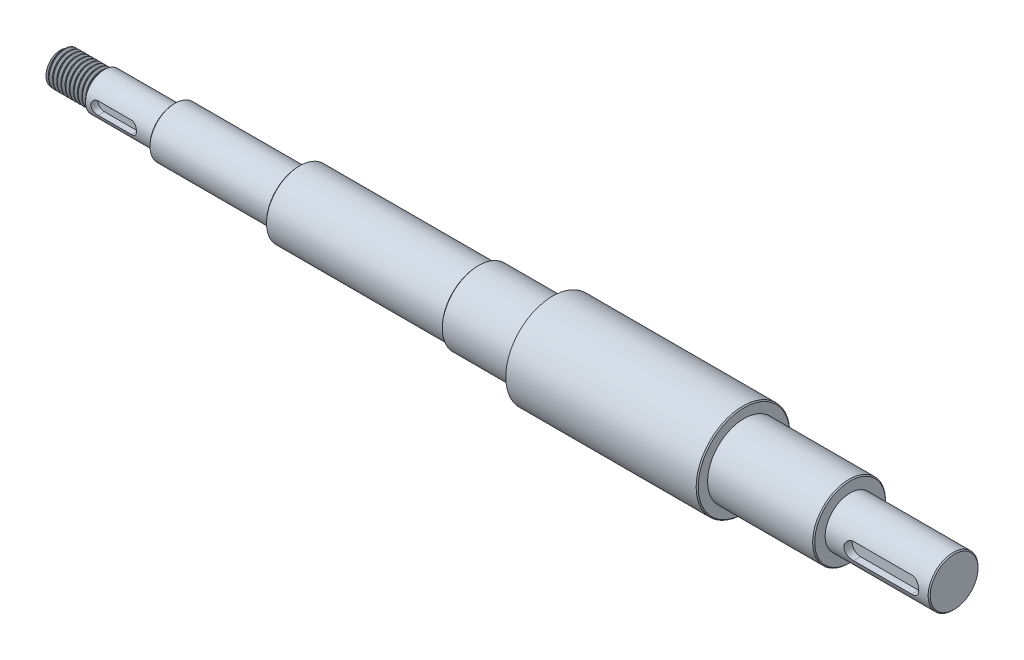
SolidWorks part; units mm, degrees
note: The reader was unsure of these and kept them because the rebuilt part matched: shared geometry of "Sketch2<3>".
ref_plane "Front Plane" through (0, 0, 0) normal (0, 0, 1) x (1, 0, 0)
ref_plane "Top Plane" through (0, 0, 0) normal (0, 1, 0) x (1, 0, 0)
ref_plane "Right Plane" through (0, 0, 0) normal (1, 0, 0) x (0, 0, -1)
sketch "Sketch1" plane through (0, 0, 0) normal (0, 0, 1) x (1, 0, 0)
  line L0 (-214.5, 0) -> (214.5, 0) construction
  line L1 (-214.5, 0) -> (-214.5, 8)
  line L2 (-214.5, 8) -> (-194.5, 8)
  line L3 (-194.5, 8) -> (-194.5, 9)
  line L4 (-194.5, 9) -> (-160.5, 9)
  line L5 (-160.5, 9) -> (-160.5, 12)
  line L6 (-160.5, 12) -> (-100.5, 12)
  line L7 (-100.5, 12) -> (-100.5, 16)
  line L8 (-100.5, 16) -> (-14.5, 16)
  line L9 (-14.5, 16) -> (-14.5, 17.5)
  line L10 (-14.5, 17.5) -> (21.5, 17.5)
  line L11 (21.5, 17.5) -> (21.5, 22.5)
  line L12 (21.5, 22.5) -> (113.5, 22.5)
  line L13 (113.5, 22.5) -> (113.5, 17.5)
  line L14 (113.5, 17.5) -> (164.5, 17.5)
  line L15 (164.5, 17.5) -> (164.5, 12)
  line L16 (164.5, 12) -> (214.5, 12)
  line L17 (214.5, 12) -> (214.5, 0)
  line L18 (214.5, 0) -> (-214.5, 0)
  point P4 (0, 0)
  dimension "D1" = 429
  dimension "D2" = 20
  dimension "D3" = 34
  dimension "D4" = 60
  dimension "D5" = 86
  dimension "D6" = 36
  dimension "D7" = 92
  dimension "D8" = 51
  dimension "D9" = 50
  dimension "D10" = 16
  dimension "D11" = 18
  dimension "D12" = 24
  dimension "D13" = 32
  dimension "D14" = 35
  dimension "D15" = 45
  dimension "D16" = 35
  dimension "D17" = 24
revolve "Revolve1" add sketch "Sketch1" angle 360 about L0
chamfer "Chamfer1" distance 0.5 angle 45 8 edges at (113.5, 0, 22.5) (-214.5, 0, 8) (-194.5, 0, 9) (-160.5, 0, 12) (-100.5, 0, 16) (-14.5, 0, 17.5) (164.5, 0, 17.5) (214.5, 0, 12)
thread "Thread3" pitch 2 start angle 0, offset 1.5, length 20, pitch 2, diameter 16
ref_plane "Plane4" through (-215.5, 0, -8) normal (0, -1, 0) x (0, 0, -1)
sketch "Thread Profile4" plane through (-215.5, 0, -8) normal (0, -1, 0) x (0, 0, -1)
  line L0 (0, 0) -> (0, 2) construction
  line L11 (0, 0) -> (0, 1.75)
  line L12 (0, 1.75) -> (-1.0825, 1.125)
  line L13 (-1.0825, 1.125) -> (-1.0825, 0.625)
  line L15 (-1.0825, 0.625) -> (0, 0)
  line L17 (-1.0825, 0.875) -> (0, 0.875) construction
  point P2 (0, 0)
  dimension "Pitch" = 2
  dimension "Profile_Angle" = 60
  dimension "Profile_Land" = 0.5
  dimension "Profile_Height" = 1.0825
sketch "Sketch2" plane through (0, 0, 0) normal (0, 0, 1) x (1, 0, 0)
  line L0 (-188.5, 0) -> (-172.5, 0) construction
  line L1 (-188.5, 3) -> (-172.5, 3)
  line L2 (-188.5, -3) -> (-172.5, -3)
  line L3 (-160.5, 0) -> (-194, 0) construction
  line L4 (-194.5, 8.5) -> (-194.5, -8.5) construction
  line L5 (214.5, -11.5) -> (214.5, 11.5) construction
  line L8 (177.5, 0) -> (205.5, 0) construction
  line L9 (177.5, 4) -> (205.5, 4)
  line L10 (177.5, -4) -> (205.5, -4)
  arc A0 (-188.5, 3) -> (-188.5, -3) centre (-188.5, 0) ccw
  arc A1 (-172.5, -3) -> (-172.5, 3) centre (-172.5, 0) ccw
  arc A2 (177.5, 4) -> (177.5, -4) centre (177.5, 0) ccw
  arc A3 (205.5, -4) -> (205.5, 4) centre (205.5, 0) ccw
  point P2 (-180.5, 0)
  point P11 (191.5, 0)
  dimension "D1" = 6
  dimension "D3" = 3
  dimension "D4" = 9
  dimension "D6" = 4
  dimension "D2" = 16
  dimension "D5" = 28
extrude "Cut-Extrude5" cut sketch "Sketch2" along normal blind 3.5 from offset 5.5 contours L2 A1 L1 A0
extrude "Cut-Extrude6" cut sketch "Sketch2<3>" along normal blind 4 from offset 8
sketch "Sketch2<3>" plane through (0, 0, 0) normal (0, 0, 1) x (1, 0, 0) same geometry as "Sketch2"
